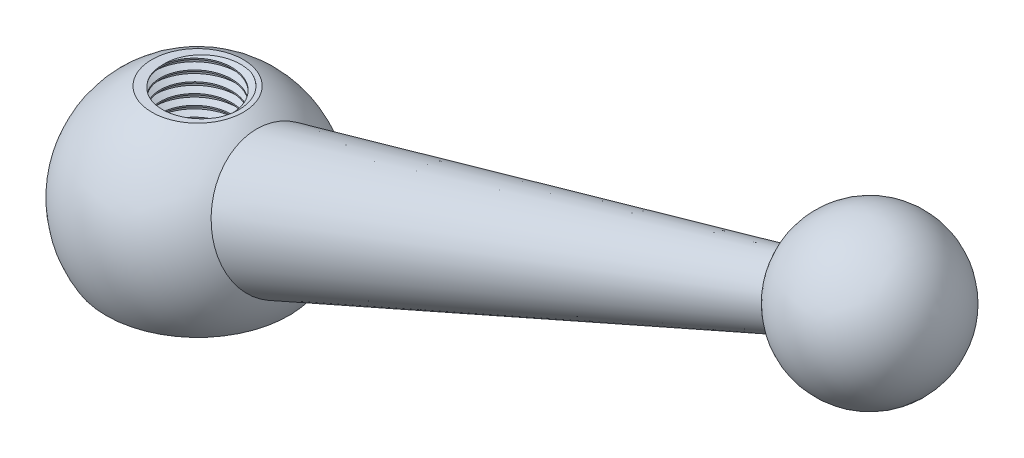
SolidWorks part; units mm, degrees
ref_plane "Front Plane" through (0, 0, 0) normal (0, 0, 1) x (1, 0, 0)
ref_plane "Top Plane" through (0, 0, 0) normal (0, 1, 0) x (1, 0, 0)
ref_plane "Right Plane" through (0, 0, 0) normal (1, 0, 0) x (0, 0, -1)
sketch "Sketch1" plane through (0, 0, 0) normal (0, 0, 1) x (1, 0, 0)
  line L0 (0, 0) -> (50000, 0) construction
  line L1 (0, 0) -> (46984.631, 17101.0072) construction
  line L2 (-17.8885, -11) -> (17.8885, -11) construction
  line L3 (8.9443, 19) -> (-8.9443, 19) construction
  line L4 (11.5816, 17.5176) -> (116.5862, 48.819)
  line L5 (-19.7335, -7.1824) -> (145.6524, 53.0131)
  circle A0 centre (131.557, 47.8828) radius 15
  circle A1 centre (0, 0) radius 21
  point P13 (117.1115, 51.9237)
  point P16 (12.8194, 19)
  point P19 (0, 0)
  dimension "D2" = 30
  dimension "D3" = 42
  dimension "D1" = 20
  dimension "D4" = 11
  dimension "D5" = 140
  dimension "D6" = 30
  dimension "D7" = 12
  dimension "D8" = 25
revolve "Revolve1" add sketch "Sketch1" angle 360 about L1 region at (-3.0483, 8.3752, 0) region at (60.8639, 27.2934, 0) region at (129.3796, 53.8651, 0)
sketch "Sketch2" plane through (0, 0, 0) normal (0, 0, 1) x (1, 0, 0)
  line L0 (-22.8592, -11) -> (24.9832, -11)
  line L1 (-31.5805, 19) -> (12.043, 19)
  line L2 (-31.5805, 19) -> (-31.5805, 25.6523)
  line L3 (-31.5805, 25.6523) -> (12.043, 25.6523)
  line L4 (12.043, 25.6523) -> (12.043, 19)
  line L5 (-22.8592, -11) -> (-22.8592, -22.9325)
  line L6 (-22.8592, -22.9325) -> (24.9832, -22.9325)
  line L7 (24.9832, -22.9325) -> (24.9832, -11)
  dimension "D1" = 11
  dimension "D2" = 30
extrude "Cut-Extrude1" cut sketch "Sketch2" against normal through all both and the other way through all
hole_wizard "M16x2.0 Tapped Hole1" positions "Sketch3" profile "Sketch4" tap size "M16x2.0" standard "ANSI Metric" end condition through all
sketch "Sketch3" plane through (0, -11, 0) normal (0, -1, 0) x (-1, 0, 0)
  point P0 (0, 0)
sketch "Sketch4" plane through (0, -11, 0) normal (1, 0, 0) x (0, 0, -1)
  line L0 (0, 0) -> (0, 73.8828)
  line L1 (0, 73.8828) -> (7, 73.8828)
  line L2 (7, 73.8828) -> (7, 0)
  line L5 (7, 0) -> (0, 0)
  line L11 (0, -6.35) -> (0, 107.95) construction
  dimension "Thru Tap Drill Dia." = 14
  dimension "Thru Tap Drill Depth" = 73.8828
cosmetic thread "Hole Thread1" parameters "D2"=16
thread "Thread1" pitch 2 method cut trim with start face yes trim with end face yes profile "Thread Profile1" start angle 0, offset 5, length 40, pitch 2, diameter 14
ref_plane "Plane1" through (7, -16, 0) normal (0, 0, -1) x (-1, 0, 0)
sketch "Thread Profile1" plane through (7, -16, 0) normal (0, 0, -1) x (-1, 0, 0)
  line L0 (0, 0) -> (0, 2) construction
  line L11 (0, 0) -> (0, 1.75)
  line L12 (0, 1.75) -> (-1.0825, 1.125)
  line L13 (-1.0825, 1.125) -> (-1.0825, 0.625)
  line L15 (-1.0825, 0.625) -> (0, 0)
  line L17 (-1.0825, 0.875) -> (0, 0.875) construction
  point P2 (0, 0)
  dimension "Pitch" = 2
  dimension "Profile_Angle" = 60
  dimension "Profile_Land" = 0.5
  dimension "Profile_Height" = 1.0825
